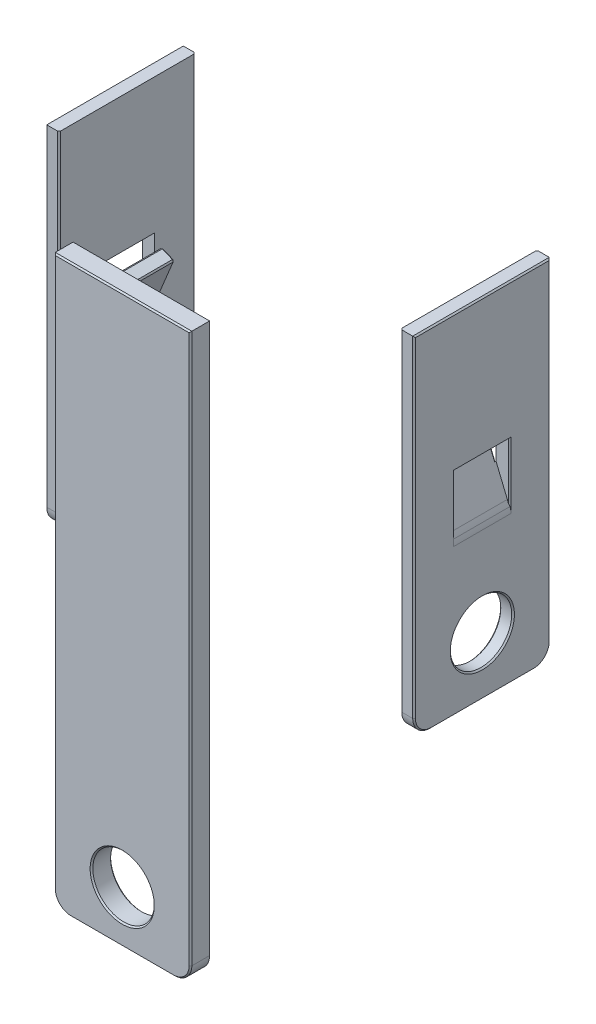
SolidWorks part; units mm, degrees
ref_plane "Front Plane" through (0, 0, 0) normal (0, 0, 1) x (1, 0, 0)
ref_plane "Top Plane" through (0, 0, 0) normal (0, 1, 0) x (1, 0, 0)
ref_plane "Right Plane" through (0, 0, 0) normal (1, 0, 0) x (0, 0, -1)
sketch "Sketch1" plane through (0, 0, 0) normal (0, 1, 0) x (1, 0, 0)
  circle A0 centre (0, 0) radius 3
extrude "Boss-Extrude1" add sketch "Sketch1" along normal blind 4.5
sketch "Sketch2" plane through (0, 0, 0) normal (0, -1, 0) x (1, 0, 0)
  circle A0 centre (0, 0) radius 4
extrude "Boss-Extrude3" add sketch "Sketch2" along normal blind 5.7
sketch "Sketch3" plane through (0, -5.7, 0) normal (0, -1, 0) x (1, 0, 0)
  circle A0 centre (0, 0) radius 3.875
extrude "Boss-Extrude4" add sketch "Sketch3" along normal blind 6
sketch "Sketch4" plane through (0, 4.5, 0) normal (0, 1, 0) x (1, 0, 0)
  circle A0 centre (0, 0) radius 1.75
extrude "Cut-Extrude1" cut sketch "Sketch4" against normal blind 15
sketch "Sketch5" plane through (0, -11.7, 0) normal (0, -1, 0) x (1, 0, 0)
  line L0 (-2.7, 0) -> (2.7, 0) construction
  line L1 (0, 0) -> (0, 3.875) construction
  line L2 (-2.5, 1) -> (-2.5, -1)
  line L3 (-2.7, -1) -> (-2.5, -1)
  line L4 (2.7, 1) -> (2.5, 1)
  line L5 (2.7, 1) -> (2.7, -1)
  line L6 (2.7, -1) -> (2.5, -1)
  line L7 (2.5, 1) -> (2.5, -1)
  line L8 (-2.7, 1) -> (-2.7, -1)
  line L9 (-2.7, 1) -> (-2.5, 1)
  circle A1 centre (0, 0) radius 3.875 construction
  point P3 (0, 0)
  point P12 (2.7, 0)
extrude "Boss-Extrude5" add sketch "Sketch5" along normal blind 3.1
sketch "Sketch6" plane through (0, -11.7, 0) normal (0, -1, 0) x (1, 0, 0)
  line L0 (0, 3.875) -> (0, 2.275) construction
  line L3 (1, 2.275) -> (-1, 2.275)
  line L4 (1, 2.275) -> (1, 2.575)
  line L5 (1, 2.575) -> (-1, 2.575)
  line L6 (-1, 2.275) -> (-1, 2.575)
  circle A0 centre (0, 0) radius 3.875 construction
  circle A1 centre (0, 0) radius 3.875 construction
  point P10 (0, 2.275)
extrude "Boss-Extrude6" add sketch "Sketch6" along normal blind 6.3
fillet "Fillet1" radius 0.25 6 edges at (-1, -18, 2.425) (1, -18, 2.425) (-2.6, -14.8, -1) (-2.6, -14.8, 1) (2.6, -14.8, 1) (2.6, -14.8, -1)
sketch "Sketch7" plane through (-2.7, 0, 0) normal (-1, 0, 0) x (0, 0, 1)
  line L0 (0, -11.7) -> (0, -14.8) construction
  line L1 (1, -11.7) -> (-1, -11.7) construction
  line L2 (0.75, -14.8) -> (-0.75, -14.8) construction
  line L3 (-0.4, -11.7) -> (-0.4, -12.6)
  line L4 (-0.4, -11.7) -> (0.4, -11.7)
  line L6 (-0.4, -12.6) -> (0.4, -12.6)
  line L7 (0.4, -11.7) -> (0.4, -12.6)
  circle A0 centre (0, -13.9534) radius 0.45
  point P13 (0, -12.6)
extrude "Cut-Extrude2" cut sketch "Sketch7" against normal blind 6.3
sketch "Sketch8" plane through (0, 0, 2.275) normal (0, 0, -1) x (-1, 0, 0)
  line L0 (0, -11.7) -> (0, -18) construction
  line L1 (1, -11.7) -> (-1, -11.7) construction
  line L2 (0.75, -18) -> (-0.75, -18) construction
  circle A0 centre (0, -17.242) radius 0.45
extrude "Cut-Extrude3" cut sketch "Sketch8" against normal blind 6.3
sketch "Sketch9" plane through (0, 0, 0) normal (0, 0, 1) x (1, 0, 0)
  line L1 (4.8528, -11.7) -> (-5.4907, -11.7)
  line L2 (4.8528, -11.7) -> (4.8528, 7.8467)
  line L3 (4.8528, 7.8467) -> (-5.4907, 7.8467)
  line L4 (-5.4907, -11.7) -> (-5.4907, 7.8467)
extrude "Cut-Extrude4" cut sketch "Sketch9" against normal through all both and the other way through all
ref_plane "Plane1" through (0, -11.7, 0) normal (0, 1, 0) x (1, 0, 0)
sketch "Sketch10" plane through (0, -11.7, 0) normal (0, 1, 0) x (1, 0, 0)
  line L0 (0, -2.275) -> (0, 3.1787) construction
  line L1 (-1, -2.275) -> (1, -2.275) construction
  line L2 (2.5, 1) -> (2.5, -1)
  line L3 (-2.7, 1) -> (-2.5, 1)
  line L4 (-2.7, 1) -> (-2.7, -1)
  line L5 (-2.7, -1) -> (-2.5, -1)
  line L6 (-2.5, 1) -> (-2.5, -1)
  line L7 (2.7, -1) -> (2.5, -1)
  line L8 (2.7, 1) -> (2.7, -1)
  line L9 (2.7, 1) -> (2.5, 1)
  line L11 (-1, -2.275) -> (1, -2.275)
  line L12 (-1, -2.275) -> (-1, -2.575)
  line L13 (-1, -2.575) -> (1, -2.575)
  line L14 (1, -2.275) -> (1, -2.575)
extrude "Boss-Extrude12" add sketch "Sketch10" along normal blind 2
sketch "Sketch11" plane through (0, 0, 0.4) normal (0, 0, -1) x (-1, 0, 0)
  line L0 (2.5, -12.6) -> (2.2012, -11.8757)
  line L1 (2.5, -12.6) -> (2.5, -11.7) construction
  line L2 (2.6849, -12.5237) -> (2.3861, -11.7994)
  line L4 (2.2012, -11.8757) -> (2.3861, -11.7994)
  line L5 (2.6849, -12.5237) -> (2.7, -12.6)
  line L6 (2.7, -12.6) -> (2.5, -12.6)
  line L7 (0, -17.242) -> (0, -9.7689) construction
  line L8 (-2.7, -12.6) -> (-2.5, -12.6)
  line L9 (-2.6849, -12.5237) -> (-2.7, -12.6)
  line L10 (-2.2012, -11.8757) -> (-2.3861, -11.7994)
  line L11 (-2.6849, -12.5237) -> (-2.3861, -11.7994)
  line L12 (-2.5, -12.6) -> (-2.2012, -11.8757)
  dimension "D1" = 0.2
extrude "Boss-Extrude13" add sketch "Sketch11" along normal up to surface (0.8 mm away) up to face at (-2.6, -12.15, -0.4)
fillet "Fillet2" radius 0.5 3 edges at (-2.6849, -12.5237, 0) (-2.7, -12.6, 0) (-2.5, -12.6, 0)
fillet "Fillet3" radius 0.5 3 edges at (2.5, -12.6, 0) (2.6849, -12.5237, 0) (2.7, -12.6, 0)
chamfer "Chamfer1" distance 0.02 angle 45 14 edges at (0.9268, -17.9268, 2.275) (1, -13.725, 2.275) (0, -9.7, 2.275) (-1, -13.725, 2.275) (-0.9268, -17.9268, 2.275) (0, -18, 2.275) (-0.45, -17.242, 2.275) (0, -9.7, 2.575) (1, -13.725, 2.575) (0.9268, -17.9268, 2.575) (0, -18, 2.575) (-0.9268, -17.9268, 2.575) (-1, -13.725, 2.575) (-0.45, -17.242, 2.575)
chamfer "Chamfer2" distance 0.02 angle 45 27 edges at (-2.7, -12.1745, -0.4) (-2.7, -11.7, 0) (-2.7, -12.1745, 0.4) (-2.7, -14.7268, 0.9268) (-2.7, -14.8, 0) (-2.7, -14.7268, -0.9268) (-2.7, -12.125, -1) (-2.7, -9.7, 0) (-2.7, -12.125, 1) (-2.5, -13.9534, 0.45) (-2.7, -13.9534, 0.45) (-2.5, -11.7, 0) (-2.4905, -12.6019, 0.4) (-2.4905, -12.6019, -0.4) (-2.2937, -11.8376, 0.4) (-2.4431, -11.9375, 0.4) (-2.3861, -11.7994, 0) (-2.3317, -12.1921, 0.4) (-2.2012, -11.8757, 0) (-2.3317, -12.1921, -0.4) (-2.2937, -11.8376, -0.4) (-2.4431, -11.9375, -0.4) (-2.5, -12.125, -1) (-2.5, -12.125, 1) (-2.5, -14.7268, -0.9268) (-2.5, -14.7268, 0.9268) (-2.5, -14.8, 0)
chamfer "Chamfer3" distance 0.02 angle 45 27 edges at (2.5, -13.9534, -0.45) (2.7, -14.7268, -0.9268) (2.7, -14.8, 0) (2.7, -14.7268, 0.9268) (2.7, -12.125, 1) (2.7, -9.7, 0) (2.7, -12.125, -1) (2.7, -13.9534, 0.45) (2.7, -12.1745, -0.4) (2.7, -11.7, 0) (2.7, -12.1745, 0.4) (2.4905, -12.6019, 0.4) (2.4905, -12.6019, -0.4) (2.3861, -11.7994, 0) (2.4431, -11.9375, 0.4) (2.2937, -11.8376, 0.4) (2.3317, -12.1921, 0.4) (2.2012, -11.8757, 0) (2.3317, -12.1921, -0.4) (2.2937, -11.8376, -0.4) (2.4431, -11.9375, -0.4) (2.5, -11.7, 0) (2.5, -12.125, 1) (2.5, -12.125, -1) (2.5, -14.7268, 0.9268) (2.5, -14.7268, -0.9268) (2.5, -14.8, 0)
